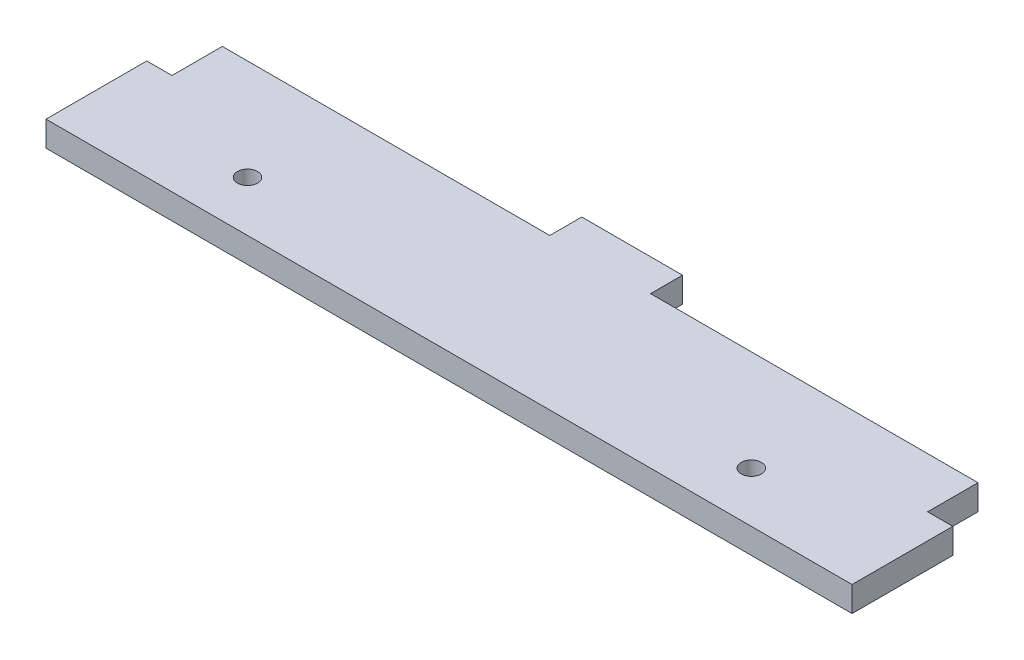
SolidWorks part; units mm, degrees
ref_plane "Front Plane" through (0, 0, 0) normal (0, 0, 1) x (1, 0, 0)
ref_plane "Top Plane" through (0, 0, 0) normal (0, 1, 0) x (1, 0, 0)
ref_plane "Right Plane" through (0, 0, 0) normal (1, 0, 0) x (0, 0, -1)
sketch "Sketch1" plane through (0, 0, 0) normal (0, 1, 0) x (1, 0, 0)
  line L0 (-80, -18.175) -> (80, -18.175)
  line L1 (80, -18.175) -> (80, 1.825)
  line L2 (80, 1.825) -> (75, 1.825)
  line L3 (75, 1.825) -> (75, 11.825)
  line L4 (75, 11.825) -> (10, 11.825)
  line L5 (10, 11.825) -> (10, 18.175)
  line L6 (10, 18.175) -> (-10, 18.175)
  line L7 (-10, 18.175) -> (-10, 11.825)
  line L8 (-10, 11.825) -> (-75, 11.825)
  line L9 (-75, 11.825) -> (-75, 1.825)
  line L10 (-75, 1.825) -> (-80, 1.825)
  line L11 (-80, 1.825) -> (-80, -18.175)
  line L12 (0, 18.175) -> (0, -18.175) construction
  line L13 (-50, -8.175) -> (50, -8.175) construction
  circle A0 centre (-50, -8.175) radius 2
  circle A1 centre (50, -8.175) radius 2
  point P20 (0, -8.175)
  dimension "D7" = 4
  dimension "D1" = 10
  dimension "D2" = 20
  dimension "D3" = 6.35
  dimension "D4" = 5
  dimension "D5" = 150
  dimension "D6" = 20
  dimension "D8" = 10
  dimension "D9" = 100
extrude "Boss-Extrude1" add sketch "Sketch1" along normal mid plane 5
